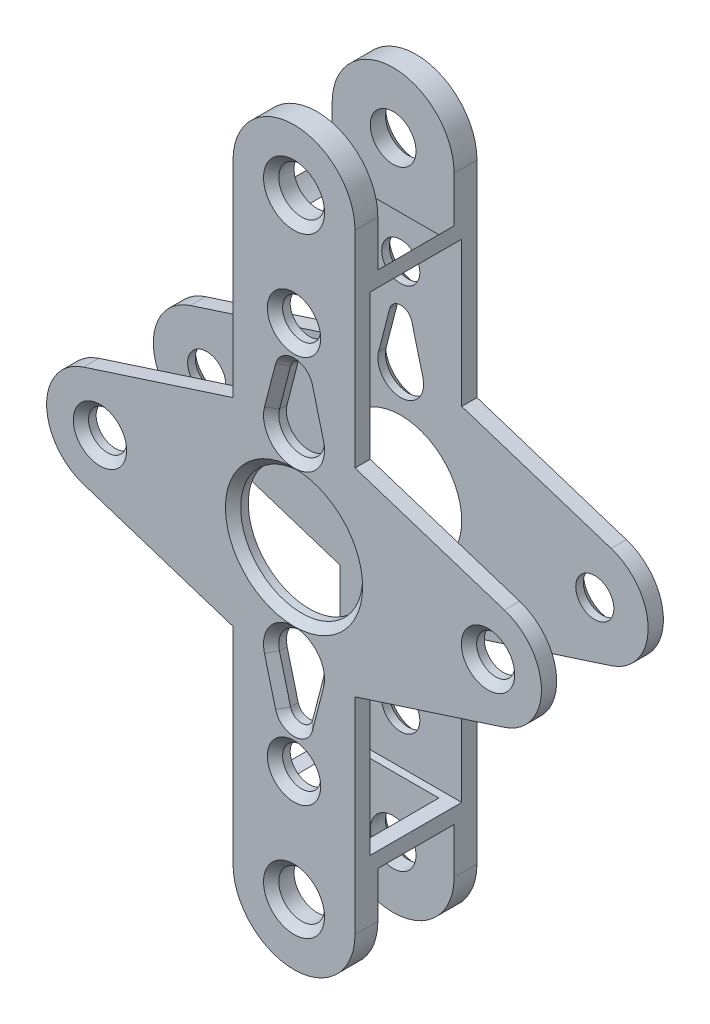
SolidWorks part; units mm, degrees
material "尼龙 101"
ref_plane "前视基准面" through (0, 0, 0) normal (0, 0, 1) x (1, 0, 0)
ref_plane "上视基准面" through (0, 0, 0) normal (0, 1, 0) x (1, 0, 0)
ref_plane "右视基准面" through (0, 0, 0) normal (1, 0, 0) x (0, 0, -1)
sketch "草图1" plane through (0, 0, 0) normal (0, 0, 1) x (1, 0, 0)
  line L0 (0, -12.7279) -> (0, 12.7279) construction
  line L5 (-7.2168, 0) -> (6.3795, 0) construction
  line L7 (0, 0) -> (0, -12.7279) construction
  line L8 (0, 0) -> (-12.7279, 0) construction
  line L9 (-4, 20) -> (-4, 6.5)
  line L10 (-4, 6.5) -> (-13.8046, 3.3303)
  line L11 (-4, -20) -> (-4, -6.5)
  line L12 (-4, -6.5) -> (-13.8046, -3.3303)
  line L13 (4, 20) -> (4, 6.5)
  line L14 (4, 6.5) -> (13.8046, 3.3303)
  line L15 (4, -6.5) -> (13.8046, -3.3303)
  line L16 (4, -20) -> (4, -6.5)
  circle A4 centre (0, 12.7279) radius 1.25
  circle A5 centre (0, -12.7279) radius 1.25
  circle A6 centre (-12.7279, 0) radius 1.25
  circle A7 centre (12.7279, 0) radius 1.25
  arc A8 (-13.8046, 3.3303) -> (-13.8046, -3.3303) centre (-12.7279, 0) ccw
  arc A10 (13.8046, -3.3303) -> (13.8046, 3.3303) centre (12.7279, 0) ccw
  circle A12 centre (0, 20) radius 1.5
  circle A13 centre (0, -20) radius 1.5
  arc A14 (4, 20) -> (-4, 20) centre (0, 20) ccw
  arc A15 (-4, -20) -> (4, -20) centre (0, -20) ccw
  circle A16 centre (0, 12.7279) radius 3.5 [skipped]
  circle A17 centre (0, -12.7279) radius 3.5 [skipped]
  point P25 (0, 0)
  dimension "D1" = 2.5
  dimension "D2" = 18
  dimension "D5" = 7
  dimension "D7" = 3
  dimension "D8" = 40
  dimension "D9" = 8
  dimension "D3" = 2
  dimension "D10" = 6.5
  dimension "D6" = 4
extrude "凸台-拉伸1" add sketch "草图1" along normal mid plane 8
sketch "草图2" plane through (0, 0, 4) normal (0, 0, 1) x (1, 0, 0)
  line L0 (0, 0) -> (16.2545, 0) construction
  line L1 (0, 0) -> (0, 20) construction
  line L2 (-0.7262, 9.6875) -> (-1.4524, 6.875)
  line L3 (0.7262, 9.6875) -> (1.4524, 6.875)
  line L4 (-0.7262, -9.6875) -> (-1.4524, -6.875)
  line L5 (0.7262, -9.6875) -> (1.4524, -6.875)
  circle A0 centre (0, 0) radius 4
  arc A1 (-1.4524, 6.875) -> (1.4524, 6.875) centre (0, 6.5) ccw
  arc A2 (0.7262, 9.6875) -> (-0.7262, 9.6875) centre (0, 9.5) ccw
  arc A3 (-1.4524, -6.875) -> (1.4524, -6.875) centre (0, -6.5) cw
  arc A4 (0.7262, -9.6875) -> (-0.7262, -9.6875) centre (0, -9.5) cw
  dimension "D1" = 8
  dimension "D2" = 3
  dimension "D3" = 1.5
  dimension "D4" = 3
  dimension "D5" = 10.5
extrude "切除-拉伸1" cut sketch "草图2" against normal through all
chamfer "倒角1" distance 0.5 angle 45 30 edges at (1.5, -20, 4) (1.25, -12.7279, 4) (13.9779, 0, 4) (1.5, 20, 4) (1.25, 12.7279, 4) (-11.4779, 0, 4) (0, -10.25, 4) (1.0893, -8.2812, 4) (-1.0893, -8.2812, 4) (-1.0893, 8.2812, 4) (0, 10.25, 4) (1.0893, 8.2812, 4) (4, 0, 4) (1.25, -12.7279, -4) (0, -10.25, -4) (1.0893, -8.2812, -4) (-1.0893, -8.2812, -4) (1.5, -20, -4) (1.5, 20, -4) (-1.0893, 8.2812, -4) (0, 10.25, -4) (1.0893, 8.2812, -4) (1.25, 12.7279, -4) (-11.4779, 0, -4) (13.9779, 0, -4) (4, 0, -4) (0, 5, -4) (0, -5, -4) (0, -5, 4) (0, 5, 4)
sketch "草图3" plane through (0, 0, 0) normal (0, 0, 1) x (1, 0, 0)
  circle A0 centre (0, 20) radius 5
  circle A1 centre (0, -20) radius 5
  dimension "D1" = 10
extrude "切除-拉伸2" cut sketch "草图3" against normal mid plane 5
sketch "草图7" plane through (0, 0, 0) normal (1, 0, 0) x (0, 0, -1)
  line L0 (2.5, 17) -> (-2.5, 17) construction
  line L1 (-3, -16) -> (3, -16)
  line L2 (-3, -16) -> (-3, 16)
  line L3 (-3, 16) -> (3, 16)
  line L4 (3, -16) -> (3, 16)
  line L5 (-3, -16) -> (3, 16) construction
  line L6 (-3, 16) -> (3, -16) construction
  point P0 (0, 0)
  dimension "D1" = 1
  dimension "D2" = 6
extrude "切除-拉伸4" cut sketch "草图7" against normal through all both and the other way through all
